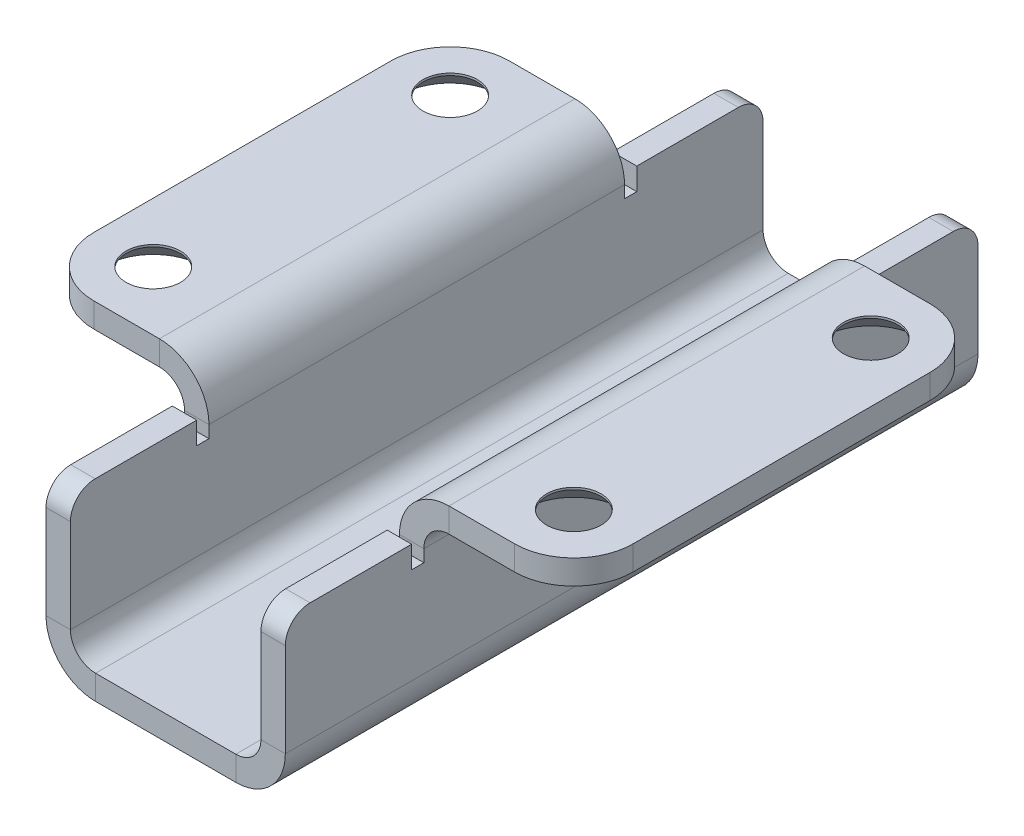
SolidWorks part; units mm, degrees
note: The reader was unsure of these and kept them because the rebuilt part matched: flange length of "Edge-Flange1", "Edge-Flange2".
ref_plane "Front Plane" through (0, 0, 0) normal (0, 0, 1) x (1, 0, 0)
ref_plane "Top Plane" through (0, 0, 0) normal (0, 1, 0) x (1, 0, 0)
ref_plane "Right Plane" through (0, 0, 0) normal (1, 0, 0) x (0, 0, -1)
sketch "Sketch1" plane through (0, 0, 0) normal (0, 1, 0) x (1, 0, 0)
  line L0 (0, 70) -> (0, -70) construction
  line L1 (-19.25, -70) -> (19.25, -70)
  line L2 (-19.25, -70) -> (-19.25, 70)
  line L3 (-19.25, 70) -> (19.25, 70)
  line L4 (19.25, -70) -> (19.25, 70)
  line L5 (-19.25, -70) -> (19.25, 70) construction
  line L6 (-19.25, 70) -> (19.25, -70) construction
  point P0 (0, 0)
  dimension "D1" = 140
  dimension "D2" = 38.5
base flange "Base-Flange1" sketch "Sketch1" thickness 4.9352 reverse thickness direction no parameters "D1"=5.08
edge flange "Edge-Flange1" sketch "Sketch11" flange angle 90 flange length 37 flange position material outside bend radius 5.08 thickness 4.9352 relief rectangular parameters "D6"=10, "D8"=1
sketch "Sketch11" plane through (-19.25, 0, 0) normal (-1, 0, 0) x (0, 0, 1)
  line L0 (-70, 0) -> (70, 0) construction
  line L1 (-70, 0) -> (70, 0)
  line L2 (-70, 0) -> (-70, 37)
  line L3 (-70, 37) -> (70, 37)
  line L4 (70, 37) -> (70, 0)
bend "EdgeBend2" bend radius 5.08 bend angle 90 parameters "D5"=2
edge flange "Edge-Flange2" sketch "Sketch19" flange angle 90 flange length 30.3148 flange position material inside bend radius 5.08 thickness 4.9352 relief rectangular parameters "D6"=10
sketch "Sketch19" plane through (-24.1852, 37, 0) normal (0, 1, 0) x (0, 0, -1)
  line L0 (-70, 0) -> (70, 0) construction
  line L1 (-42, 0) -> (42, 0)
  line L2 (-42, 0) -> (-42, 30.3148)
  line L3 (-42, 30.3148) -> (42, 30.3148)
  line L4 (42, 30.3148) -> (42, 0)
  line L5 (70, -4.9352) -> (-70, -4.9352) construction
  point P6 (0, 0)
  point P7 (0, 0)
  dimension "D1" = 84
  dimension "D2" = 35.25
bend "EdgeBend4" bend radius 5.08 bend angle 90 parameters "D5"=3
fillet "Fillet1" radius 12 2 edges at (-54.5, 34.5324, -42) (-54.5, 34.5324, 42)
sketch "Sketch20" plane through (-24.1852, 0, 0) normal (-1, 0, 0) x (0, 0, 1)
  line L0 (-44.4676, 37) -> (-44.4676, 24.5172) construction
  line L1 (-70, 37) -> (-44.4676, 37)
  line L2 (-70, 37) -> (-70, 29)
  line L3 (-70, 29) -> (-44.4676, 29)
  line L4 (-44.4676, 37) -> (-44.4676, 29)
  line L5 (44.4676, 24.5172) -> (44.4676, 37) construction
  line L6 (70, 37) -> (44.4676, 37)
  line L7 (70, 37) -> (70, 29)
  line L8 (70, 29) -> (44.4676, 29)
  line L9 (44.4676, 37) -> (44.4676, 29)
  dimension "D1" = 8
extrude "Cut-Extrude1" cut sketch "Sketch20" against normal up to next normal cut yes
fillet "Fillet2" radius 5 2 edges at (-21.7176, 29, -70) (-21.7176, 29, 70)
mirror "Mirror1" about plane through (0, 0, 0) normal (1, 0, 0) of "Cut-Extrude1", "Edge-Flange1", "Edge-Flange2", "Fillet1", "Fillet2"
bend "MirrorBend3" bend radius 5.08 bend angle 90 parameters "D5"=8
bend "MirrorBend4" bend radius 5.08 bend angle 90 parameters "D5"=9
sketch "Sketch24" plane through (0, 32.0648, 0) normal (0, -1, 0) x (1, 0, 0)
  line L1 (-42.5, -30) -> (42.5, -30) construction
  line L2 (-42.5, -30) -> (-42.5, 30) construction
  line L3 (-42.5, 30) -> (42.5, 30) construction
  line L4 (42.5, -30) -> (42.5, 30) construction
  line L5 (-42.5, -30) -> (42.5, 30) construction
  line L6 (-42.5, 30) -> (42.5, -30) construction
  point P0 (0, 0)
  point P1 (42.5, 30)
  point P2 (-42.5, -30)
  point P3 (-42.5, 30)
  point P4 (42.5, -30)
  point P16 (0, 0)
  point P22 (-42.5, 30)
  point P24 (-42.5, -30)
  point P26 (42.5, -30)
  point P28 (42.5, 30)
  dimension "D1" = 60
  dimension "D2" = 85
hole_wizard "CSK for M10 Flat Head Machine Screw1" positions "Sketch24" profile "Sketch30" countersink size "M10" standard "ANSI Metric" end condition through all
sketch "Sketch30" plane through (42.5, 32.0648, 30) normal (1, 0, 0) x (0, 0, -1)
  line L0 (0, 0) -> (0, 4.9352)
  line L1 (0, 4.9352) -> (5.5, 4.9352)
  line L2 (5.5, 4.9352) -> (5.5, 4.5)
  line L3 (5.5, 4.5) -> (10, 0)
  line L5 (10, 0) -> (0, 0)
  line L6 (-5.5, 4.5) -> (-10, 0) construction
  line L11 (0, -6.35) -> (0, 107.95) construction
  dimension "Thru Hole Dia." = 11
  dimension "Thru Hole Depth" = 4.9352
  dimension "Near C'Sink Dia." = 20
  dimension "Near C'Sink Angle" = 90
sketch "Bend-Lines1" [suppressed] plane through (0, 0, 0) normal (0, 1, 0) x (1, 0, 0)
sketch "Bounding-Box1" [suppressed] plane through (0, 0, 0) normal (0, 1, 0) x (1, 0, 0)
sheet metal parameters "Sheet-Metal1" thickness 4.9352 parameters "D1"=5.08
flat pattern "Flat-Pattern1" [suppressed]
sketch "Bend-Lines2" plane through (0, 0, 0) normal (0, 1, 0) x (1, 0, 0)
sketch3d "Bounding-Box2" [suppressed]
  line L0 (50, -50, 0) -> (50, 50, 0) construction
  line L1 (-50, -50, 0) -> (-50, 50, 0) construction
  line L2 (50, -50, 0) -> (-50, -50, 0) construction
  line L3 (50, 50, 0) -> (-50, 50, 0) construction
sheet metal parameters "Sheet-Metal2" thickness 4.9352 parameters "D1"=5.08
flat pattern "Flat-Pattern1" [suppressed]
sketch "Bend-Lines2" plane through (0, 0, 0) normal (0, 1, 0) x (1, 0, 0)
  line L0 (-13.5479, 50) -> (-13.5479, -50) construction
  line L2 (-13.5479, 50) -> (-13.5479, -50) construction
sketch3d "Bounding-Box2" [suppressed]
  line L0 (-36.3958, -50, 0) -> (-36.3958, 50, 0) construction
  line L1 (12.7, -50, 0) -> (12.7, 50, 0) construction
  line L2 (-36.3958, -50, 0) -> (12.7, -50, 0) construction
  line L3 (-36.3958, 50, 0) -> (12.7, 50, 0) construction
bend of the flat pattern "Flatten-<EdgeBend2>1"
sheet metal parameters "Sheet-Metal3" thickness 4.9352 parameters "D1"=5.08
flat pattern "Flat-Pattern1"
sketch "Bend-Lines2" plane through (0, 0, 0) normal (0, 1, 0) x (1, 0, 0)
  line L0 (-13.5479, 50) -> (-13.5479, -50) construction
  line L2 (-13.5479, 50) -> (-13.5479, -50) construction
  line L6 (-32.3084, 30) -> (-32.3084, -30) construction
  line L7 (-32.3084, 30) -> (-32.3084, -30) construction
sketch3d "Bounding-Box2" [suppressed]
  line L0 (12.7, -50, 0) -> (12.7, 50, 0) construction
  line L1 (-58.5563, -50, 0) -> (-58.5563, 50, 0) construction
  line L2 (12.7, -50, 0) -> (-58.5563, -50, 0) construction
  line L3 (12.7, 50, 0) -> (-58.5563, 50, 0) construction
bend of the flat pattern "Flatten-<EdgeBend4>1"
bend of the flat pattern "Flatten-<EdgeBend2>1"
sheet metal parameters "Sheet-Metal4" thickness 4.9352 parameters "D1"=5.08
flat pattern "Flat-Pattern1" [suppressed]
sketch "Bend-Lines2" plane through (0, 0, 0) normal (0, 1, 0) x (1, 0, 0)
  line L0 (-20.0979, 70) -> (-20.0979, -70) construction
  line L1 (53.8584, -40) -> (53.8584, 40) construction
  line L2 (-20.0979, 70) -> (-20.0979, -70) construction
  line L3 (20.0979, -70) -> (20.0979, 70) construction
  line L4 (53.8584, -40) -> (53.8584, 40) construction
  line L5 (20.0979, -70) -> (20.0979, 70) construction
  line L6 (-53.8584, 40) -> (-53.8584, -40) construction
  line L7 (-53.8584, 40) -> (-53.8584, -40) construction
sketch3d "Bounding-Box2" [suppressed]
  line L0 (-81.7711, 70, 0) -> (81.7711, 70, 0) construction
  line L1 (-81.7711, -70, 0) -> (81.7711, -70, 0) construction
  line L2 (-81.7711, 70, 0) -> (-81.7711, -70, 0) construction
  line L3 (81.7711, 70, 0) -> (81.7711, -70, 0) construction
bend of the flat pattern "Flatten-<EdgeBend4>1"
bend of the flat pattern "Flatten-<EdgeBend2>1"
sketch "Sketch24-2" [suppressed] plane through (-30.5211, -4.9352, 0) normal (0, -1, 0) x (1, 0, 0)
  line L1 (-42.5, -30) -> (42.5, -30) construction
  line L2 (-42.5, -30) -> (-42.5, 30) construction
  line L3 (-42.5, 30) -> (42.5, 30) construction
  line L4 (42.5, -30) -> (42.5, 30) construction
  line L5 (-42.5, -30) -> (42.5, 30) construction
  line L6 (-42.5, 30) -> (42.5, -30) construction
  point P0 (0, 0)
  point P1 (42.5, 30)
  point P2 (-42.5, -30)
  point P3 (-42.5, 30)
  point P4 (42.5, -30)
  point P16 (0, 0)
  dimension "D1" = 60
  dimension "D2" = 85
bend of the flat pattern "Flatten-<MirrorBend3>1"
bend of the flat pattern "Flatten-<MirrorBend4>1"
sheet metal parameters "Sheet-Metal5" thickness 4.9352 parameters "D1"=5.08
flat pattern "Flat-Pattern1"
sketch "Bend-Lines2" plane through (0, 0, 0) normal (0, 1, 0) x (1, 0, 0)
  line L0 (-13.5479, 50) -> (-13.5479, -50) construction
  line L2 (-13.5479, 50) -> (-13.5479, -50) construction
  line L6 (-32.3084, 30) -> (-32.3084, -30) construction
  line L7 (-32.3084, 30) -> (-32.3084, -30) construction
sketch3d "Bounding-Box2" [suppressed]
  line L0 (-58.5563, -50, 0) -> (-58.5563, 50, 0) construction
  line L1 (12.7, -50, 0) -> (12.7, 50, 0) construction
  line L2 (-58.5563, -50, 0) -> (12.7, -50, 0) construction
  line L3 (-58.5563, 50, 0) -> (12.7, 50, 0) construction
bend of the flat pattern "Flatten-<EdgeBend4>1"
bend of the flat pattern "Flatten-<EdgeBend2>1"
sheet metal parameters "Sheet-Metal7" thickness 4.9352 parameters "D1"=5.08
flat pattern "Flat-Pattern1" [suppressed]
sketch "Bend-Lines2" plane through (0, 0, 0) normal (0, 1, 0) x (1, 0, 0)
  line L0 (-20.0979, 70) -> (-20.0979, -70) construction
  line L2 (-20.0979, 70) -> (-20.0979, -70) construction
  line L6 (-53.8584, 42) -> (-53.8584, -42) construction
  line L7 (-53.8584, 42) -> (-53.8584, -42) construction
  line L8 (53.8584, -42) -> (53.8584, 42) construction
  line L9 (20.0979, -70) -> (20.0979, 70) construction
  line L10 (53.8584, -42) -> (53.8584, 42) construction
  line L11 (20.0979, -70) -> (20.0979, 70) construction
sketch3d "Bounding-Box2" [suppressed]
  line L0 (-85.0211, 70, 0) -> (85.0211, 70, 0) construction
  line L1 (-85.0211, -70, 0) -> (85.0211, -70, 0) construction
  line L2 (-85.0211, 70, 0) -> (-85.0211, -70, 0) construction
  line L3 (85.0211, 70, 0) -> (85.0211, -70, 0) construction
bend of the flat pattern "Flatten-<EdgeBend4>1"
bend of the flat pattern "Flatten-<EdgeBend2>1"
bend of the flat pattern "Flatten-<MirrorBend3>2"
bend of the flat pattern "Flatten-<MirrorBend4>2"
sketch "Sketch24-2" plane through (-30.5211, -4.9352, 0) normal (0, -1, 0) x (1, 0, 0)
  line L1 (-42.5, -30) -> (42.5, -30) construction
  line L2 (-42.5, -30) -> (-42.5, 30) construction
  line L3 (-42.5, 30) -> (42.5, 30) construction
  line L4 (42.5, -30) -> (42.5, 30) construction
  line L5 (-42.5, -30) -> (42.5, 30) construction
  line L6 (-42.5, 30) -> (42.5, -30) construction
  point P0 (0, 0)
  point P1 (42.5, 30)
  point P2 (-42.5, -30)
  point P3 (-42.5, 30)
  point P4 (42.5, -30)
  point P16 (0, 0)
  point P22 (-42.5, 30)
  point P24 (-42.5, -30)
  point P26 (42.5, -30)
  point P28 (42.5, 30)
  dimension "D1" = 60
  dimension "D2" = 85
